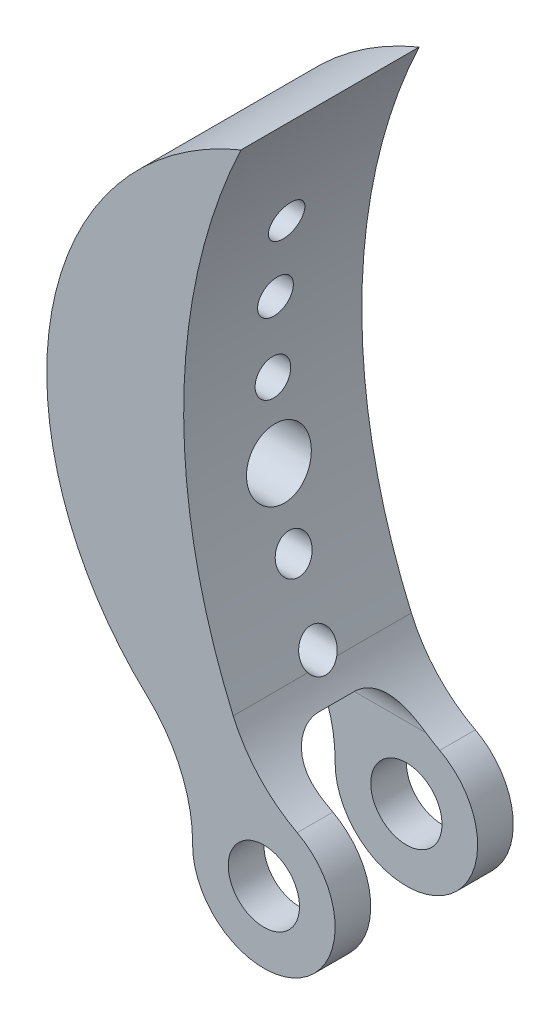
SolidWorks part; units mm, degrees
ref_plane "前视基准面" through (0, 0, 0) normal (0, 0, 1) x (1, 0, 0)
ref_plane "上视基准面" through (0, 0, 0) normal (0, 1, 0) x (1, 0, 0)
ref_plane "右视基准面" through (0, 0, 0) normal (1, 0, 0) x (0, 0, -1)
other "Configuration Table"
sketch "Sketch1" plane through (0, 0, 0) normal (0, 0, 1) x (1, 0, 0)
  line L0 (-5, 0) -> (-5, 5)
  line L1 (0, 0) -> (0, 5)
  line L2 (0, 5) -> (-5, 5)
  circle A0 centre (0, 0) radius 5
  circle A1 centre (0, 0) radius 2.5
  dimension "D1" = 5
  dimension "D2" = 10
  dimension "D3" = 5
extrude "Boss-Extrude1" add sketch "Sketch1" along normal mid plane 12.5 contours A0 L1 L2 L0 | A1 A0 region at (-3.8832, 3.8832, 0) region at (-3.4355, 3.4355, 0)
sketch "Sketch2" plane through (0, 0, 6.25) normal (0, 0, 1) x (1, 0, 0)
  line L0 (0, 5) -> (-5, 5) construction
  line L3 (0, 5) -> (6.766, 23.5893) construction
  line L4 (0, 5) -> (36.3731, 26) construction
  line L5 (0, 7.5) -> (0, 5) construction
  line L6 (-5, 5) -> (0, 5)
  arc A1 (-5, 0) -> (0, 5) centre (0, 0) ccw construction
  arc A2 (-5, 5) -> (-1.6053, 43.9344) centre (6.766, 23.5893) cw
  arc A3 (-1.6053, 43.9344) -> (0, 5) centre (36.3731, 26) ccw
  dimension "D1" = 42
  dimension "D2" = 22
  dimension "D3" = 20
  dimension "D4" = 40
extrude "Boss-Extrude2" add sketch "Sketch2" against normal up to surface (12.5 mm away) up to face at (-1.3215, 1.3215, -6.25)
fillet "Fillet2" radius 10 1 edges at (-5, 5, 0)
fillet "Fillet3" radius 10 1 edges at (0, 5, 0)
sketch "Sketch3" plane through (0, 0, 0) normal (1, 0, 0) x (0, 0, -1)
  line L2 (-6.25, -5) -> (6.25, -5) construction
  line L3 (0, -5) -> (0, 20) construction
  circle A0 centre (0, 20) radius 2.25
  circle A3 centre (0, 5) radius 1.25
  circle A4 centre (0, 10) radius 1.25
  circle A5 centre (0, 15) radius 1.25
  circle A6 centre (0, 20) radius 1.25
  circle A7 centre (0, 25) radius 1.25
  circle A8 centre (0, 30) radius 1.25
  circle A9 centre (0, 35) radius 1.25
  circle A10 centre (0, 40) radius 1.25
  dimension "D1" = 4.5
  dimension "D4" = 2.5
  dimension "D2" = 25
  dimension "D3" = 5
  dimension "D6" = 5
  dimension "D5" = 8
extrude "Cut-Extrude1" cut sketch "Sketch3" against normal through all contours A6 | A0 A6 | A8 | A9 | A7 | L3 A5 | A5 L3 | A4 L3 | L3 A4 | L3 A3 | A3 L3 region at (0, 5, 0.5305) region at (0, 20.8589, 0.8589) region at (0, 21.546, 1.546) region at (0, 15, 0.5305) region at (0, 15, -0.5305) region at (0, 10, 0.5305) region at (0, 10, -0.5305) region at (0, 5, -0.5305) region at (0, 25, 0) region at (0, 30, 0) region at (0, 35, 0)
sketch "Sketch5" plane through (0, 0, 0) normal (1, 0, 0) x (0, 0, -1)
  line L1 (-3.75, -7.5) -> (3.75, -7.5)
  line L2 (-3.75, -7.5) -> (-3.75, 7.5)
  line L3 (-3.75, 7.5) -> (3.75, 7.5)
  line L4 (3.75, -7.5) -> (3.75, 7.5)
  line L5 (-3.75, -7.5) -> (3.75, 7.5) construction
  line L6 (-3.75, 7.5) -> (3.75, -7.5) construction
  point P0 (0, 0)
  dimension "D1" = 7.5
  dimension "D2" = 15
extrude "Cut-Extrude2" cut sketch "Sketch5" against normal through all both and the other way through all
fillet "Fillet5" radius 2.5 2 edges at (-4.6978, 7.5, -3.75) (-4.6978, 7.5, 3.75)
sketch "Sketch18" plane through (0, 7.5, 0) normal (0, -1, 0) x (1, 0, 0)
  line L0 (-8.2385, 0) -> (-5.7385, 0) construction
  line L1 (-8.2385, 1.25) -> (-8.2385, -1.25) construction
  circle A0 centre (-5.7385, 0) radius 1.25
  dimension "D1" = 2.5
  dimension "D2" = 2.5
extrude "Cut-Extrude4" cut sketch "Sketch18" against normal blind 5
sketch "Sketch20" plane through (0, 0, 6.25) normal (0, 0, 1) x (1, 0, 0)
  line L0 (0, 0) -> (5, 0) construction
  line L1 (0, 0) -> (5.3033, 5.3033) construction
  arc A0 (-5, 0) -> (2.3401, 4.4186) centre (0, 0) ccw construction
  circle A3 centre (5.3033, 5.3033) radius 1.25
  circle A4 centre (5.3033, 5.3033) radius 2.5
  circle A5 centre (0, 0) radius 5
  circle A6 centre (0, 0) radius 2.5
  circle A7 centre (0, 0) radius 2.5 construction
  arc A8 (4.8296, -1.2941) -> (7.3055, 3.8062) centre (19.3185, -5.1764) cw
  arc A9 (-1.2941, 4.8296) -> (3.8062, 7.3055) centre (-5.1764, 19.3185) ccw
  arc M4 (-5, 0) -> (2.3401, 4.4186) centre (0, 0) ccw
  arc M5 (2.3401, 4.4186) -> (-2.1524, 9.2732) centre (7.0203, 13.2558) cw
  circle M9 centre (0, 0) radius 2.5
  dimension "D2" = 2.5
  dimension "D3" = 5
  dimension "D5" = 15
  dimension "D1" = 45
  dimension "D4" = 7.5
extrude "Boss-Extrude3" [suppressed] add sketch "Sketch20" against normal blind 2.5 contours A5 M4 M9 | A9 A4 M5 M4 | A9 A5 M5 | A4 A3 | A5 A8 A4
mirror "Mirror1" [suppressed] about plane through (0, 0, 0) normal (0, 0, 1)
